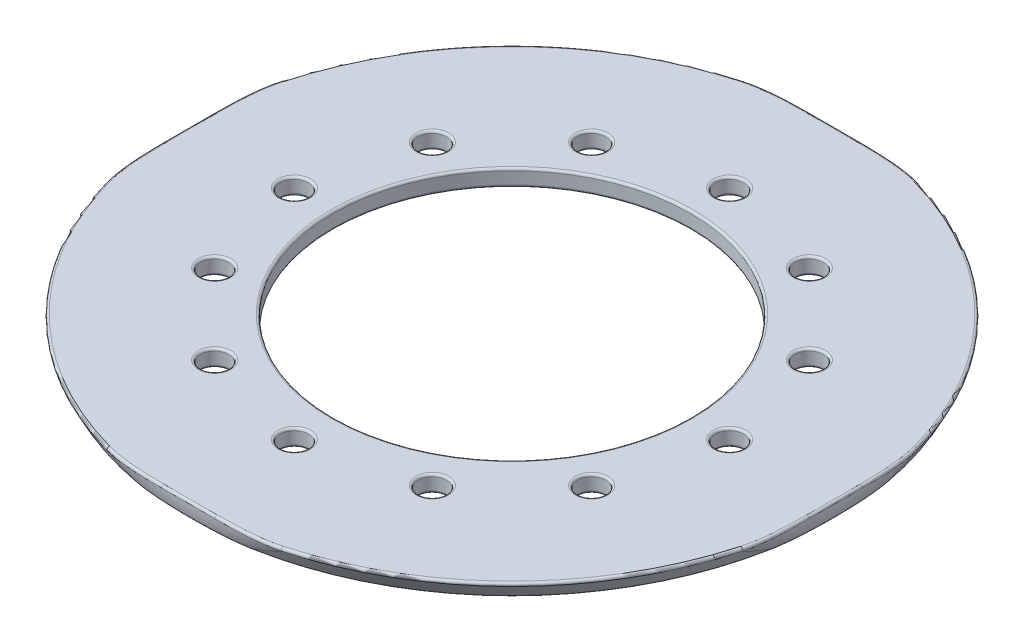
SolidWorks part; units mm, degrees
ref_plane "Front Plane" through (0, 0, 0) normal (0, 0, 1) x (1, 0, 0)
ref_plane "Top Plane" through (0, 0, 0) normal (0, 1, 0) x (1, 0, 0)
ref_plane "Right Plane" through (0, 0, 0) normal (1, 0, 0) x (0, 0, -1)
sketch "Main Revolve Sketch" plane through (0, 0, 0) normal (0, 0, 1) x (1, 0, 0)
  line L0 (0, 0) -> (0, 13.75)
  line L1 (0, 13.75) -> (0, 96.25)
  line L2 (0, 0) -> (0, -13.75)
  line L3 (-82.5, -13.75) -> (-82.5, 13.75)
  line L4 (0, -13.75) -> (0, -96.25)
  line L5 (-82.5, 0) -> (0, 0) construction
  arc A0 (0, 96.25) -> (-82.5, 13.75) centre (0, 13.75) ccw
  arc A1 (-82.5, -13.75) -> (0, -96.25) centre (0, -13.75) ccw
  dimension "D2" = 82.5
  dimension "D3" = 82.5
  dimension "D1" = 82.5
  dimension "D4" = 13.75
revolve "Main Revolve" add sketch "Main Revolve Sketch" angle 360 about L1
sketch "Top Cut Sketch" plane through (0, 0, 0) normal (0, 1, 0) x (1, 0, 0)
  line L1 (-186.2466, 173.137) -> (257.6713, 173.137)
  line L2 (-186.2466, 173.137) -> (-186.2466, -194.8356)
  line L3 (-186.2466, -194.8356) -> (257.6713, -194.8356)
  line L4 (257.6713, 173.137) -> (257.6713, -194.8356)
extrude "Top Cut" cut sketch "Top Cut Sketch" against normal blind 50 and the other way through all
sketch "Bolt Hole Cut Sketch" plane through (0, 0, 0) normal (0, 1, 0) x (1, 0, 0)
  line L0 (-57.5, 0) -> (-40, 0) construction
  circle A0 centre (-48.75, 0) radius 3.1563
  circle A2 centre (0, 0) radius 57.5 construction
  circle A3 centre (0, 0) radius 40 construction
  dimension "D2" = 6.3125
  dimension "D1" = 80
  dimension "D3" = 115
extrude "Bolt Hole Cut" cut sketch "Bolt Hole Cut Sketch" against normal through all both and the other way through all
pattern_circular "Bolt Hole Circular Pattern" count 12 over 360 about axis through (0, -50, 0) along (0, 1, 0) of "Bolt Hole Cut"
ref_plane "Side Cut Plane" through (0, 0, 72.5) normal (0, 0, 1) x (1, 0, 0)
sketch "Side Cut Sketch" plane through (0, 0, 72.5) normal (0, 0, 1) x (1, 0, 0)
  line L1 (-180.9911, 11.665) -> (163.0254, 11.665)
  line L2 (-180.9911, 11.665) -> (-180.9911, -134.3285)
  line L3 (-180.9911, -134.3285) -> (163.0254, -134.3285)
  line L4 (163.0254, 11.665) -> (163.0254, -134.3285)
extrude "Side Cut" cut sketch "Side Cut Sketch" along normal through all
sketch "Center Cut Sketch" plane through (0, 0, 0) normal (0, 1, 0) x (1, 0, 0)
  circle A0 centre (0, 0) radius 40
  dimension "D1" = 80
extrude "Center Cut" cut sketch "Center Cut Sketch" against normal through all
pattern_circular "CirPattern1" count 4 over 360 about axis through (0, -50, 0) along (0, 1, 0) of "Side Cut"
ref_plane "Bottom Plane" through (0, -85.9043, 0) normal (0, -1, 0) x (-1, 0, 0)
sketch "Bottom Cut Sketch" plane through (0, -85.9043, 0) normal (0, -1, 0) x (-1, 0, 0)
  line L0 (-72.5, 15.3603) -> (-72.5, -15.3603) construction
  line L1 (-97.5, 97.5) -> (97.5, 97.5)
  line L2 (-97.5, 97.5) -> (-97.5, -97.5)
  line L3 (-97.5, -97.5) -> (97.5, -97.5)
  line L4 (97.5, 97.5) -> (97.5, -97.5)
  line L5 (72.5, -15.3603) -> (72.5, 15.3603) construction
  line L6 (15.3603, 72.5) -> (-15.3603, 72.5) construction
  line L7 (-15.3603, -72.5) -> (15.3603, -72.5) construction
  dimension "D1" = 25
  dimension "D2" = 25
  dimension "D3" = 25
  dimension "D4" = 25
extrude "Bottom Cut" cut sketch "Bottom Cut Sketch" against normal offset from surface (32.1543 mm away) 3.75 up to face at (0, -50, 40)
fillet "Fillet1" radius 10 4 edges at (72.5, -53.12, 0) (0, -53.12, -72.5) (-72.5, -53.12, 0) (0, -53.12, 72.5)
fillet "Fillet2" radius 0.5 47 edges at (-48.75, -53.75, 3.1563) (-42.2187, -53.75, -21.2187) (0, -53.75, -45.5938) (42.2187, -53.75, -21.2188) (42.2187, -53.75, 27.5312) (0, -53.75, 51.9062) (0, -53.75, 40) (51.0208, -53.75, -51.0208) (8.0322, -53.75, -71.6404) (-51.0208, -53.75, -51.0208) (-71.6404, -53.75, -8.0322) (-51.0208, -53.75, 51.0208) (-8.0322, -53.75, 71.6404) (51.0208, -53.75, 51.0208) (71.6404, -53.75, 8.0322) (-24.375, -53.75, 45.375) (24.375, -53.75, 45.375) (48.75, -53.75, 3.1563) (24.375, -53.75, -39.0625) (-24.375, -53.75, -39.0625) (-42.2187, -53.75, 27.5313) (-52.4032, -50, 52.4032) (-52.4032, -50, -52.4032) (52.4032, -50, -52.4032) (52.4032, -50, 52.4032) (-48.75, -50, 3.1563) (-42.2187, -50, 27.5313) (-42.2187, -50, -21.2187) (-24.375, -50, -39.0625) (0, -50, -45.5938) (24.375, -50, -39.0625) (42.2187, -50, -21.2188) (48.75, -50, 3.1563) (42.2187, -50, 27.5312) (24.375, -50, 45.375) (0, -50, 51.9062) (-24.375, -50, 45.375) (0, -50, 40) (0, -50, 72.5) (-72.5, -50, 0) (0, -50, -72.5) (72.5, -50, 0)
equation "\"D1@Main Revolve Sketch\" = \"BODY Rad\""
equation "\"D2@Main Revolve Sketch\" = \"BODY Rad\""
equation "\"D3@Main Revolve Sketch\" = \"BODY Rad\""
equation "\"D1@Side Cut Plane\" = \"BODY End Cut Rad\""
equation "\"D4@Main Revolve Sketch\" = \"BODY Height Ext\" / 2"
equation "\"D1@Bottom Cut\" = \"BODY Seal Thickness\""
equation "\"D1@Top Cut\" = \"BODY Bottom Cut Dist\""
equation "\"D2@Bolt Hole Cut Sketch\" = \"BODY Bolt Size\" + ( \"ALL Bolt Hole Off\" * \"ALL Horz Bolt Hole Off Scalar\" )"
equation "\"D1@Bolt Hole Circular Pattern\" = \"BODY Bolt Count\""
equation "\"D1@Center Cut Sketch\" = ( \"BODY End Cut Rad\" * 2 ) - ( \"ARM Rotating Bearing Thickness\" * 2 ) - ( \"BODY Nut Width\" * 2 ) - ( \"BODY Bottom Extra Nut Wall\" * 2 )"
equation "\"D1@Fillet1\" = \"ALL Big Fillet\""
equation "\"D1@Fillet2\"= \"ALL Small Fillet\""
equation "\"D1@Bolt Hole Cut Sketch\" = ( \"BODY End Cut Rad\" * 2 ) - ( \"ARM Rotating Bearing Thickness\" * 2 ) - ( \"BODY Nut Width\" * 2 ) - ( \"BODY Bottom Extra Nut Wall\" * 2 )"
equation "\"D3@Bolt Hole Cut Sketch\" = ( \"BODY End Cut Rad\" * 2 ) - ( \"ARM Rotating Bearing Thickness\" * 2 )"
equation "\"ALL Big Fillet\"= 10.0mm"
equation "\"ALL Medium Fillet\"= 1.0mm"
equation "\"ALL Small Fillet\"= 0.5mm"
equation "\"BODY Rad\"= 82.5mm"
equation "\"BODY End Cut Rad\"= 72.5mm"
equation "\"BODY Height Ext\"= 27.5mm"
equation "\"BODY Bottom Cut Dist\"= 50.0mm"
equation "\"BODY Seal Thickness\"= 3.75mm"
equation "\"BODY Wall Extra Thickness\"= 2.5mm"
equation "\"BODY Bottom Extra Nut Wall\"= 7.5mm"
equation "\"ARM Both Dia\"= 39.75mm"
equation "\"ARM Both Length\"= 67.5mm"
equation "\"ARM Both Wire Hole Dia\"= 15.0mm"
equation "\"ARM Both Prop Seal Thickness\"= 2.5mm"
equation "\"ARM Both Brass Insert Dia\"= 4.875mm"
equation "\"ARM Both Bolt Cut Depth\"= 12.5mm"
equation "\"ARM Both Nema Bolt Off\"= 15.4mm"
equation "\"ARM Both Nema Bolt Depth\"= 2.5mm"
equation "\"ARM Both Nema Width\"= 20.0mm"
equation "\"ARM Both Nema Wall Off\"= 2.5mm"
equation "\"ARM Both Nema Center Dia 1\"= 17.0mm"
equation "\"ARM Both Nema Center Dia 2\"= 10.0mm"
equation "\"ARM Both Nema Bearing OD\"= 16.0mm"
equation "\"ARM Both Nema Bearing ID\"= 10.0mm"
equation "\"ARM Both Nema Bearing Thickness\"= 4.0mm"
equation "\"ARM Both Nema Height\"= 38.0mm"
equation "\"ARM Both Nema Shaft Dia\"= 4.0mm"
equation "\"ARM Both Nema Shaft Length\"= 10.0mm"
equation "\"ARM Both Nema Center Height\"= 1.5mm"
equation "\"ARM Rotating Bearing OD\"= 68.0mm"
equation "\"ARM Rotating Bearing ID\"= 40.0mm"
equation "\"ARM Rotating Bearing Thickness\"= 15.0mm"
equation "\"ARM Static Mount Dia\"= 65.0mm"
equation "\"ARM Static Bolt Off\"= 1.125mm"
equation "\"ALL Bolt Hole Off\"= 0.25mm"
equation "\"ALL Vert Bolt Hole Off Scalar\"= 0.5mm"
equation "\"ALL Horz Bolt Hole Off Scalar\"= 1.25mm"
equation "\"ALL Nut Size Off\"= 0.25mm"
equation "\"ALL Vert Nut Off Scalar\"= 0.5mm"
equation "\"ALL Horz Nut Off Scalar\"= 1.25mm"
equation "\"BODY Bolt Count\"= 12"
equation "\"BODY Bolt Size\"= 6"
equation "\"BODY Bolt Length\"= 22.0mm"
equation "\"BODY Bolt Head Dia\"= IIF ( \"BODY Bolt Size\" = 3 , 5.75mm , IIF ( \"BODY Bolt Size\" = 4 , 7.25mm , IIF ( \"BODY Bolt Size\" = 5 , 8.75mm , IIF ( \"BODY Bolt Size\" = 6 , 10.25mm , 5.75mm ) ) ) )"
equation "\"BODY Bolt Head Height\"= IIF ( \"BODY Bolt Size\" = 3 , 3.0mm , IIF ( \"BODY Bolt Size\" = 4 , 4.0mm , IIF ( \"BODY Bolt Size\" = 5 , 5.0mm , IIF ( \"BODY Bolt Size\" = 6 , 6.0mm , 3.0mm ) ) ) )"
equation "\"BODY Nut Width\"= IIF ( \"BODY Bolt Size\" = 3 , 5.5mm , IIF ( \"BODY Bolt Size\" = 4 , 7.0mm , IIF ( \"BODY Bolt Size\" = 5 , 8.0mm , IIF ( \"BODY Bolt Size\" = 6 , 10.0mm , 5.5mm ) ) ) )"
equation "\"BODY Nut Height\"= IIF ( \"BODY Bolt Size\" = 3 , 4.0mm , IIF ( \"BODY Bolt Size\" = 4 , 5.0mm , IIF ( \"BODY Bolt Size\" = 5 , 5.0mm , IIF ( \"BODY Bolt Size\" = 6 , 6.0mm , 4.0mm ) ) ) )"
equation "\"ARM Static Bolt Count\"= 8"
equation "\"ARM Static Bolt Size\"= 5"
equation "\"ARM Static Bolt Length\"= 20.0mm"
equation "\"ARM Static Bolt Head Dia\"= IIF ( \"ARM Static Bolt Size\" = 3 , 5.75mm , IIF ( \"ARM Static Bolt Size\" = 4 , 7.25mm , IIF ( \"ARM Static Bolt Size\" = 5 , 8.75mm , IIF ( \"ARM Static Bolt Size\" = 6 , 10.25mm , 5.75mm ) ) ) )"
equation "\"ARM Static Bolt Head Height\"= IIF ( \"ARM Static Bolt Size\" = 3 , 3.0mm , IIF ( \"ARM Static Bolt Size\" = 4 , 4.0mm , IIF ( \"ARM Static Bolt Size\" = 5 , 5.0mm , IIF ( \"ARM Static Bolt Size\" = 6 , 6.0mm , 3.0mm ) ) ) )"
equation "\"ARM Static Nut Width\"= IIF ( \"ARM Static Bolt Size\" = 3 , 5.5mm , IIF ( \"ARM Static Bolt Size\" = 4 , 7.0mm , IIF ( \"ARM Static Bolt Size\" = 5 , 8.0mm , IIF ( \"ARM Static Bolt Size\" = 6 , 10.0mm , 5.5mm ) ) ) )"
equation "\"ARM Static Nut Height\"= IIF ( \"ARM Static Bolt Size\" = 3 , 4.0mm , IIF ( \"ARM Static Bolt Size\" = 4 , 5.0mm , IIF ( \"ARM Static Bolt Size\" = 5 , 5.0mm , IIF ( \"ARM Static Bolt Size\" = 6 , 6.0mm , 4.0mm ) ) ) )"
equation "\"ARM Gear Width\"= 10.0mm"
equation "\"ARM Gear Width Off\"= 2.5mm"
equation "\"ARM Gear Bolt Count\"= 4"
equation "\"ARM Gear Rotation\"= 360.0deg"
equation "\"ARM Gear Bolt Size\"= 3"
equation "\"ARM Gear Bolt Length\"= 20.0mm"
equation "\"ARM Gear Bolt Head Dia\"= IIF ( \"ARM Static Bolt Size\" = 3 , 5.75mm , IIF ( \"ARM Static Bolt Size\" = 4 , 7.25mm , IIF ( \"ARM Static Bolt Size\" = 5 , 8.75mm , IIF ( \"ARM Static Bolt Size\" = 6 , 10.25mm , 5.75mm ) ) ) )"
equation "\"ARM Gear Bolt Head Height\"= IIF ( \"ARM Static Bolt Size\" = 3 , 3.0mm , IIF ( \"ARM Static Bolt Size\" = 4 , 4.0mm , IIF ( \"ARM Static Bolt Size\" = 5 , 5.0mm , IIF ( \"ARM Static Bolt Size\" = 6 , 6.0mm , 3.0mm ) ) ) )"
equation "\"ARM Gear Nut Width\"= IIF ( \"ARM Static Bolt Size\" = 3 , 5.5mm , IIF ( \"ARM Static Bolt Size\" = 4 , 7.0mm , IIF ( \"ARM Static Bolt Size\" = 5 , 8.0mm , IIF ( \"ARM Static Bolt Size\" = 6 , 10.0mm , 5.5mm ) ) ) )"
equation "\"ARM Gear Nut Height\"= IIF ( \"ARM Static Bolt Size\" = 3 , 4.0mm , IIF ( \"ARM Static Bolt Size\" = 4 , 5.0mm , IIF ( \"ARM Static Bolt Size\" = 5 , 5.0mm , IIF ( \"ARM Static Bolt Size\" = 6 , 6.0mm , 4.0mm ) ) ) )"
equation "\"ARM Both Prop Plate Bolt Size\"= 3"
equation "\"ARM Both Prop Plate Bolt Length\"= 16.0mm"
equation "\"ARM Both Prop Plate Bolt Head Dia\"= IIF ( \"ARM Both Prop Plate Bolt Size\" = 3 , 5.75mm , IIF ( \"ARM Both Prop Plate Bolt Size\" = 4 , 7.25mm , IIF ( \"ARM Both Prop Plate Bolt Size\" = 5 , 8.75mm , IIF ( \"ARM Both Prop Plate Bolt Size\" = 6 , 10.25mm , 5.75mm ) ) ) )"
equation "\"ARM Both Prop Plate Bolt Head Height\"= IIF ( \"ARM Both Prop Plate Bolt Size\" = 3 , 3.0mm , IIF ( \"ARM Both Prop Plate Bolt Size\" = 4 , 4.0mm , IIF ( \"ARM Both Prop Plate Bolt Size\" = 5 , 5.0mm , IIF ( \"ARM Both Prop Plate Bolt Size\" = 6 , 6.0mm , 3.0mm ) ) ) )"
equation "\"ARM Both Nema Bolt Size\"= 2"
equation "\"ARM Both Nema Bolt Head Dia\"= IIF ( \"ARM Both Nema Bolt Size\" = 3 , 5.75mm , IIF ( \"ARM Both Nema Bolt Size\" = 4 , 7.25mm , IIF ( \"ARM Both Nema Bolt Size\" = 5 , 8.75mm , IIF ( \"ARM Both Nema Bolt Size\" = 6 , 10.25mm , 5.75mm ) ) ) )"
equation "\"ARM Both Nema Bolt Head Height\"= IIF ( \"ARM Both Nema Bolt Size\" = 3 , 3.0mm , IIF ( \"ARM Both Nema Bolt Size\" = 4 , 4.0mm , IIF ( \"ARM Both Nema Bolt Size\" = 5 , 5.0mm , IIF ( \"ARM Both Nema Bolt Size\" = 6 , 6.0mm , 3.0mm ) ) ) )"
